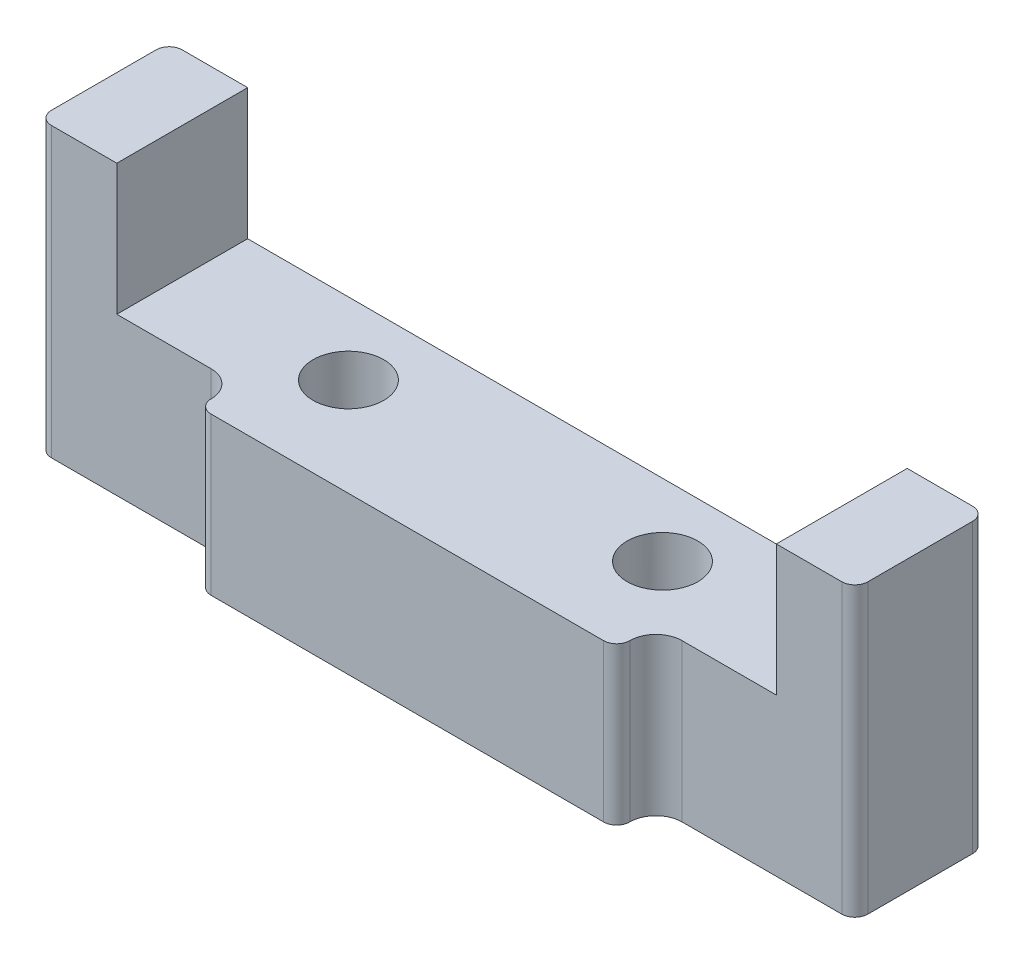
SolidWorks part; units mm, degrees
material "POM 乙缩醛共聚物"
ref_plane "前视基准面" through (0, 0, 0) normal (0, 0, 1) x (1, 0, 0)
ref_plane "上视基准面" through (0, 0, 0) normal (0, 1, 0) x (1, 0, 0)
ref_plane "右视基准面" through (0, 0, 0) normal (1, 0, 0) x (0, 0, -1)
sketch "草图1" plane through (0, 0, 0) normal (0, 0, 1) x (1, 0, 0)
  line L0 (-12.6, 2.5) -> (-15.6, 2.5)
  line L1 (12.6, -2.5) -> (-12.6, -2.5)
  line L2 (12.6, -2.5) -> (12.6, 2.5)
  line L3 (12.6, 2.5) -> (-12.6, 2.5) construction
  line L4 (-12.6, -2.5) -> (-12.6, 2.5)
  line L5 (12.6, -2.5) -> (-12.6, 2.5) construction
  line L6 (12.6, 2.5) -> (-12.6, -2.5) construction
  line L7 (-15.6, 2.5) -> (-15.6, -8.5)
  line L8 (-15.6, -8.5) -> (15.6, -8.5)
  line L9 (15.6, -8.5) -> (15.6, 2.5)
  line L10 (15.6, 2.5) -> (12.6, 2.5)
  point P0 (0, 0)
  dimension "D1" = 5
  dimension "D2" = 25.2
  dimension "D4" = 3
  dimension "D5" = 6
extrude "凸台-拉伸1" add sketch "草图1" along normal blind 5 contours L1 L4 L0 L7 L8 L9 L10 L2 region at (0, -4.7403, 0)
sketch "草图2" plane through (0, 0, 5) normal (0, 0, 1) x (1, 0, 0)
  line L0 (12.6, -2.5) -> (-12.6, -2.5) construction
  line L1 (8, -8.5) -> (-8, -8.5)
  line L2 (8, -8.5) -> (8, -2.5)
  line L3 (8, -2.5) -> (-8, -2.5)
  line L4 (-8, -8.5) -> (-8, -2.5)
  line L5 (8, -8.5) -> (-8, -2.5) construction
  line L6 (8, -2.5) -> (-8, -8.5) construction
  line L7 (0, 0) -> (0, -5.5) construction
  line L8 (-15.6, -8.5) -> (15.6, -8.5) construction
  point P0 (0, -5.5)
  dimension "D1" = 16
extrude "凸台-拉伸2" add sketch "草图2" along normal blind 1.5
sketch "草图3" plane through (0, -8.5, 0) normal (0, -1, 0) x (1, 0, 0)
  line L0 (-15.6, 2.75) -> (-6, 2.75) construction
  line L2 (0, 0) -> (0, 5.3555) construction
  line L3 (-15.6, 0) -> (15.6, 0) construction
  circle A0 centre (-6, 2.75) radius 1.35
  circle A1 centre (6, 2.75) radius 1.35
  dimension "D2" = 2.7
  dimension "D1" = 12
  dimension "D3" = 2.75
extrude "切除-拉伸1" cut sketch "草图3" against normal through all
fillet "圆角1" radius 1 2 edges at (8, -5.5, 5) (-8, -5.5, 5)
fillet "圆角2" radius 0.5 6 edges at (15.6, -3, 0) (15.6, -3, 5) (8, -5.5, 6.5) (-8, -5.5, 6.5) (-15.6, -3, 5) (-15.6, -3, 0)
